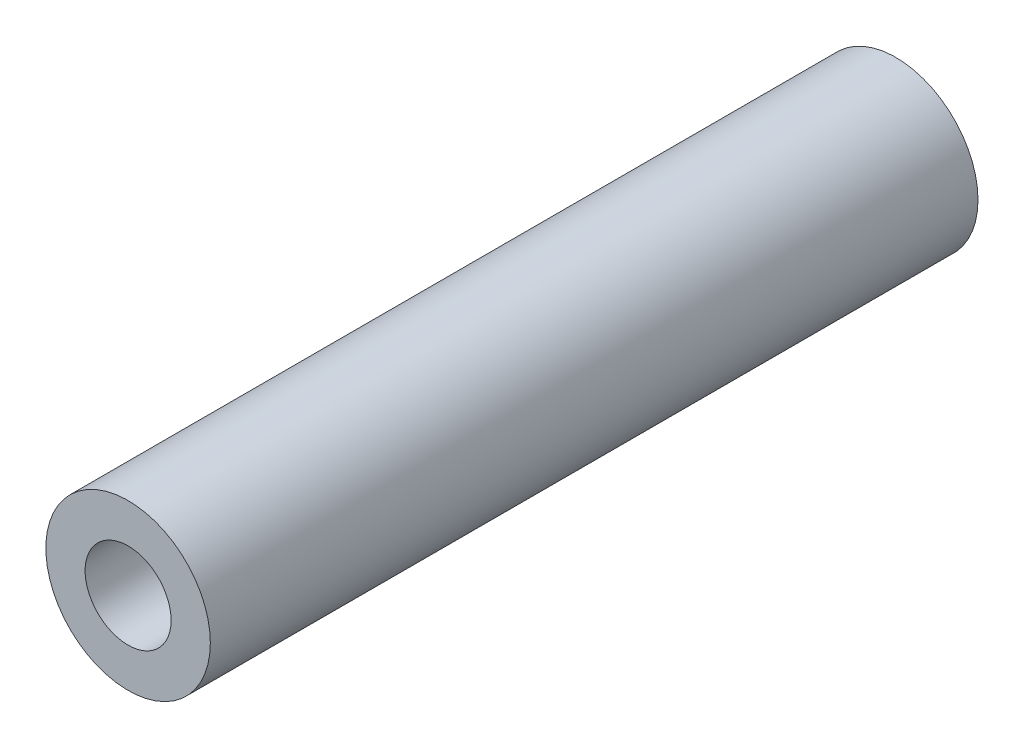
SolidWorks part; units mm, degrees
material "6061-T6 (SS)"
ref_plane "Front Plane" through (0, 0, 0) normal (0, 0, 1) x (1, 0, 0)
ref_plane "Top Plane" through (0, 0, 0) normal (0, 1, 0) x (1, 0, 0)
ref_plane "Right Plane" through (0, 0, 0) normal (1, 0, 0) x (0, 0, -1)
sketch "Sketch1" plane through (0, 0, 0) normal (0, 0, 1) x (1, 0, 0)
  circle A0 centre (0, 0) radius 2.4892
  circle A1 centre (0, 0) radius 4.7625
  dimension "D1" = 4.9784
  dimension "D2" = 9.525
extrude "Boss-Extrude1" add sketch "Sketch1" along normal blind 44.45
